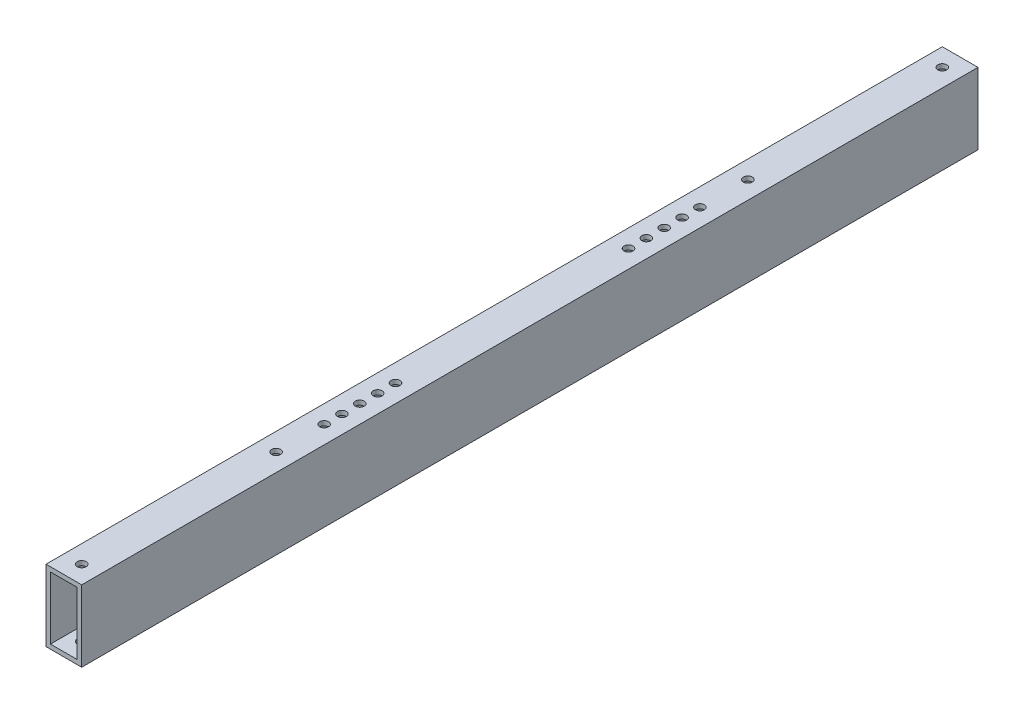
SolidWorks part; units mm, degrees
ref_plane "Front Plane" through (0, 0, 0) normal (0, 0, 1) x (1, 0, 0)
ref_plane "Top Plane" through (0, 0, 0) normal (0, 1, 0) x (1, 0, 0)
ref_plane "Right Plane" through (0, 0, 0) normal (1, 0, 0) x (0, 0, -1)
sketch "Sketch1" plane through (0, 0, 0) normal (0, 0, 1) x (1, 0, 0)
  line L0 (-9.525, 22.225) -> (9.525, 22.225)
  line L1 (-12.7, -25.4) -> (12.7, -25.4)
  line L2 (-12.7, -25.4) -> (-12.7, 25.4)
  line L3 (-12.7, 25.4) -> (12.7, 25.4)
  line L4 (12.7, -25.4) -> (12.7, 25.4)
  line L5 (-12.7, -25.4) -> (12.7, 25.4) construction
  line L6 (-12.7, 25.4) -> (12.7, -25.4) construction
  line L7 (9.525, -22.225) -> (9.525, 22.225)
  line L8 (-9.525, -22.225) -> (9.525, -22.225)
  line L9 (-9.525, -22.225) -> (-9.525, 22.225)
  point P0 (0, 0)
  dimension "D1" = 25.4
  dimension "D2" = 50.8
  dimension "D3" = 3.175
extrude "Boss-Extrude1" add sketch "Sketch1" along normal blind 637.54
sketch "Sketch2" plane through (0, 25.4, 0) normal (0, 1, 0) x (1, 0, 0)
  line L0 (0, -637.54) -> (0, 0) construction
  line L1 (12.7, -637.54) -> (-12.7, -637.54) construction
  line L2 (12.7, 0) -> (-12.7, 0) construction
  line L3 (-12.7, -318.77) -> (12.7, -318.77) construction
  line L4 (-12.7, -637.54) -> (-12.7, 0) construction
  line L5 (12.7, -637.54) -> (12.7, 0) construction
  circle A0 centre (0, -12.7) radius 3.175
  circle A1 centre (0, -151.0121) radius 3.175
  circle A2 centre (0, -486.5279) radius 3.175
  circle A3 centre (0, -624.84) radius 3.175
  circle A4 centre (0, -185.1063) radius 3.175
  circle A5 centre (0, -197.8063) radius 3.175
  circle A6 centre (0, -210.5063) radius 3.175
  circle A7 centre (0, -223.2063) radius 3.175
  circle A8 centre (0, -235.9063) radius 3.175
  circle A9 centre (0, -401.6337) radius 3.175
  circle A10 centre (0, -414.3337) radius 3.175
  circle A11 centre (0, -427.0337) radius 3.175
  circle A12 centre (0, -439.7337) radius 3.175
  circle A13 centre (0, -452.4337) radius 3.175
  dimension "D1" = 12.7
  dimension "D4" = 6.35
  dimension "D3" = 138.3121
  dimension "D5" = 172.4063
  dimension "D2" = 2
  dimension "D6" = 5
extrude "Cut-Extrude1" cut sketch "Sketch2" against normal through all
